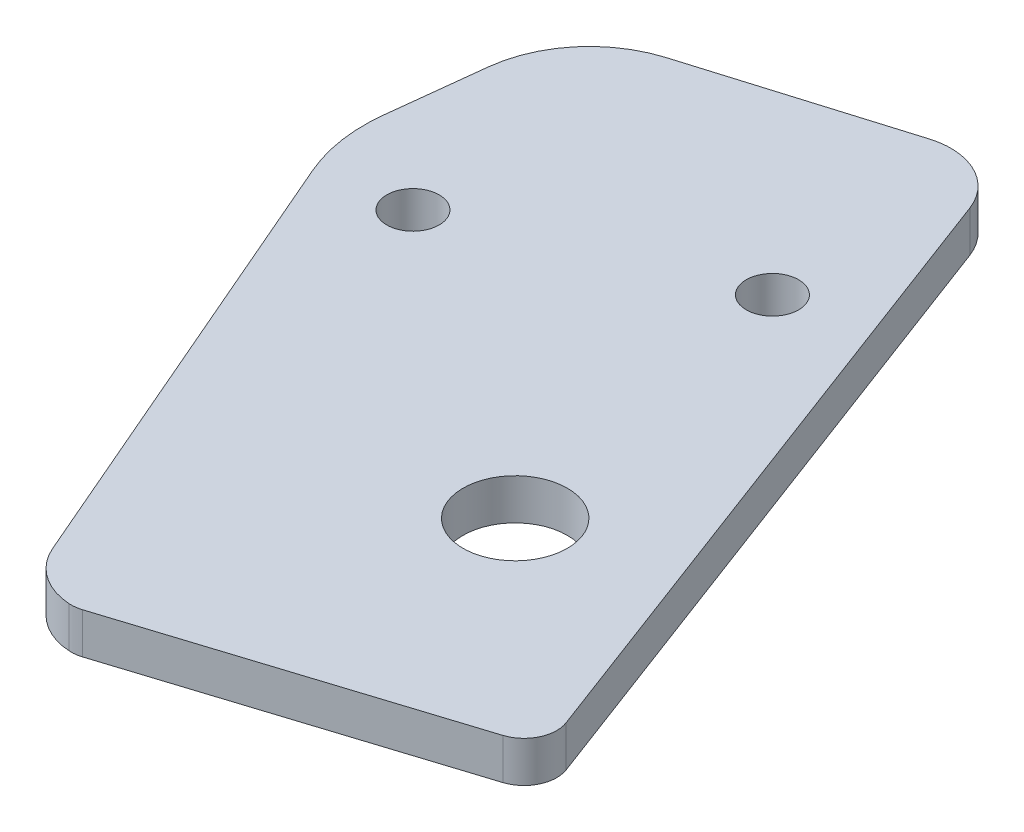
SolidWorks part; units mm, degrees
ref_plane "Front Plane" through (0, 0, 0) normal (0, 0, 1) x (1, 0, 0)
ref_plane "Top Plane" through (0, 0, 0) normal (0, 1, 0) x (1, 0, 0)
ref_plane "Right Plane" through (0, 0, 0) normal (1, 0, 0) x (0, 0, -1)
sketch "Sketch1" plane through (0, 0, 0) normal (0, 1, 0) x (1, 0, 0)
  line L0 (12.7, -6.35) -> (25.4, -6.35)
  line L1 (-12.7, -19.05) -> (12.7, -19.05)
  line L2 (-12.7, -19.05) -> (-12.7, 19.05)
  line L3 (-12.7, 19.05) -> (12.7, 19.05)
  line L4 (12.7, -19.05) -> (12.7, 19.05)
  line L5 (-12.7, -19.05) -> (12.7, 19.05) construction
  line L6 (-12.7, 19.05) -> (12.7, -19.05) construction
  line L7 (25.4, -6.35) -> (25.4, -19.05)
  line L8 (25.4, -19.05) -> (12.7, -19.05)
  point P0 (0, 0)
  dimension "D1" = 25.4
  dimension "D2" = 38.1
  dimension "D3" = 12.7
  dimension "D4" = 12.7
extrude "Boss-Extrude1" add sketch "Sketch1" along normal blind 3.175 contours L1 L4 L3 L2 | L8 L7 L0 L4 region at (19.05, 0, 12.7) region at (0, 0, 0)
sketch "Sketch2" plane through (0, 0, 0) normal (0, -1, 0) x (1, 0, 0)
  line L0 (37.3484, -5.4015) -> (58.4225, -30.0473) construction
  line L1 (58.4225, -30.0473) -> (56.4244, -36.6557) construction
  line L2 (56.4244, -36.6557) -> (28.4937, -28.211) construction
  line L3 (27.672, -14.5925) -> (16.8921, 0.2466) construction
  line L4 (18.9846, 3.1897) -> (28.6818, 0.2578) construction
  line L5 (-33.4925, -38.7551) -> (-34.3249, -31.4398) construction
  line L6 (-33.4148, -25.2954) -> (-18.0647, 10.2749) construction
  line L7 (-1.2058, -33.65) -> (-6.5286, -47.7836) construction
  line L8 (-11.9748, -50.4718) -> (-27.6795, -45.7236) construction
  line L9 (37.3484, -5.4015) -> (58.4225, -30.0473)
  line L10 (58.4225, -30.0473) -> (56.4244, -36.6557)
  line L11 (56.4244, -36.6557) -> (28.4937, -28.211)
  line L12 (27.672, -14.5925) -> (16.8921, 0.2466)
  line L13 (18.9846, 3.1897) -> (28.6818, 0.2578)
  line L14 (-33.4925, -38.7551) -> (-34.3249, -31.4398)
  line L15 (-33.4148, -25.2954) -> (-18.0647, 10.2749)
  line L16 (-1.2058, -33.65) -> (-6.5286, -47.7836)
  line L17 (-11.9748, -50.4718) -> (-27.6795, -45.7236)
  line L18 (-13.3731, 13.4695) -> (19.0101, 3.1818)
  line L20 (-25.2482, -46.4587) -> (-27.4348, -26.2567) construction
  line L21 (-13.0917, -50.1342) -> (-7.7649, -34.5071) construction
  line L22 (-34.9558, -31.5116) -> (-34.1234, -38.8269) construction
  line L23 (-27.8633, -46.3314) -> (-12.1585, -51.0797) construction
  line L24 (-5.9343, -48.0074) -> (-0.6115, -33.8738) construction
  line L25 (-18.6477, 10.5265) -> (-33.9978, -25.0438) construction
  line L26 (-34.9558, -31.5116) -> (-34.1234, -38.8269)
  line L27 (-27.8633, -46.3314) -> (-12.1585, -51.0797)
  line L28 (-5.9343, -48.0074) -> (-0.6115, -33.8738)
  line L29 (-18.6477, 10.5265) -> (-33.9978, -25.0438)
  line L31 (-0.6115, -33.8738) -> (13.9492, 4.7896)
  arc A0 (37.3484, -5.4015) -> (28.6818, 0.2578) centre (23.3524, -17.3692) ccw construction
  arc A1 (27.5335, -25.2281) -> (28.4937, -28.211) centre (29.045, -26.3876) ccw construction
  arc A2 (27.5335, -25.2281) -> (27.672, -14.5925) centre (20.4796, -19.8175) ccw construction
  arc A3 (18.9846, 3.1897) -> (16.8921, 0.2466) centre (18.4333, 1.3662) ccw construction
  arc A4 (-33.4925, -38.7551) -> (-27.6795, -45.7236) centre (-25.2904, -37.8219) ccw construction
  arc A5 (-33.4148, -25.2954) -> (-34.3249, -31.4398) centre (-22.3372, -30.0758) ccw construction
  arc A6 (-14.2611, 12.95) -> (-18.0647, 10.2749) centre (-13.9835, 8.5137) ccw construction
  arc A7 (-13.2163, 9.3838) -> (-14.2611, 12.95) centre (-14.1421, 11.0487) ccw construction
  arc A8 (-13.2163, 9.3838) -> (-2.9671, -31.0738) centre (-2.7239, -9.4851) ccw construction
  arc A9 (-1.2058, -33.65) -> (-2.9671, -31.0738) centre (-2.9886, -32.9786) ccw construction
  arc A10 (-11.9748, -50.4718) -> (-6.5286, -47.7836) centre (-10.6883, -46.2171) ccw construction
  arc A11 (37.3484, -5.4015) -> (28.6818, 0.2578) centre (23.3524, -17.3692) ccw
  arc A12 (27.5335, -25.2281) -> (28.4937, -28.211) centre (29.045, -26.3876) ccw
  arc A13 (27.5335, -25.2281) -> (27.672, -14.5925) centre (20.4796, -19.8175) ccw
  arc A14 (18.9846, 3.1897) -> (16.8921, 0.2466) centre (18.4333, 1.3662) ccw
  arc A15 (-33.4925, -38.7551) -> (-27.6795, -45.7236) centre (-25.2904, -37.8219) ccw
  arc A16 (-33.4148, -25.2954) -> (-34.3249, -31.4398) centre (-22.3372, -30.0758) ccw
  arc A17 (-14.2611, 12.95) -> (-18.0647, 10.2749) centre (-13.9835, 8.5137) ccw
  arc A18 (-13.2163, 9.3838) -> (-14.2611, 12.95) centre (-14.1421, 11.0487) ccw
  arc A19 (-13.2163, 9.3838) -> (-2.9671, -31.0738) centre (-2.7239, -9.4851) ccw
  arc A20 (-1.2058, -33.65) -> (-2.9671, -31.0738) centre (-2.9886, -32.9786) ccw
  arc A21 (-11.9748, -50.4718) -> (-6.5286, -47.7836) centre (-10.6883, -46.2171) ccw
  circle A22 centre (-2.7239, -9.4851) radius 4.05
  circle A23 centre (-7.7649, -34.5071) radius 2.032
  circle A24 centre (-27.4348, -26.2567) radius 2.032
  arc A25 (-34.1234, -38.8269) -> (-27.8633, -46.3314) centre (-25.2904, -37.8219) ccw construction
  arc A26 (-12.1585, -51.0797) -> (-5.9343, -48.0074) centre (-10.6883, -46.2171) ccw construction
  arc A27 (-0.6115, -33.8738) -> (-2.96, -30.4388) centre (-2.9886, -32.9786) ccw construction
  arc A28 (-12.9077, 8.8289) -> (-14.3007, 13.5838) centre (-14.1421, 11.0487) ccw construction
  arc A29 (-14.3007, 13.5838) -> (-18.6477, 10.5265) centre (-13.9835, 8.5137) ccw construction
  arc A30 (-33.9978, -25.0438) -> (-34.9558, -31.5116) centre (-22.3372, -30.0758) ccw construction
  arc A31 (-34.1234, -38.8269) -> (-27.8633, -46.3314) centre (-25.2904, -37.8219) ccw
  arc A32 (-12.1585, -51.0797) -> (-5.9343, -48.0074) centre (-10.6883, -46.2171) ccw
  arc A33 (-0.6115, -33.8738) -> (-2.96, -30.4388) centre (-2.9886, -32.9786) ccw
  arc A34 (-12.9077, 8.8289) -> (-14.3007, 13.5838) centre (-14.1421, 11.0487) ccw
  arc A35 (-14.3007, 13.5838) -> (-18.6477, 10.5265) centre (-13.9835, 8.5137) ccw
  arc A36 (-33.9978, -25.0438) -> (-34.9558, -31.5116) centre (-22.3372, -30.0758) ccw
  point P32 (15.495, 18.8275)
  line M1 (25.4, 19.05) -> (-12.7, 19.05)
  line M2 (-12.7, 19.05) -> (-12.7, -19.05)
  line M3 (-12.7, -19.05) -> (12.7, -19.05)
  line M4 (12.7, -19.05) -> (12.7, 6.35)
  line M5 (12.7, 6.35) -> (25.4, 6.35)
  line M6 (25.4, 6.35) -> (25.4, 19.05)
  dimension "D1" = 8.1
  dimension "D8" = 4.064
  dimension "D2" = 15.24
  dimension "D3" = 16.51
  dimension "D4" = 20.32
  dimension "D5" = 2.54
  dimension "D6" = 67
  dimension "D7" = 92
extrude "Boss-Extrude2" add sketch "Sketch2" against normal blind 3.175 contours L17 A21 L16 A20 A19 A17 L15 A16 L14 A15 M3 M2 | A19 M2 | A20 A19 M3 | L29 A36 L26 A31 L27 A32 L28 A33 A20 L16 A21 L17 A15 L14 A16 L15 A17 A18 A34 A35 M2 | A34 L18 M2 | L31 L18 M4 M5 region at (13.1164, 0, 3.8162) region at (-12.865, 0, 13.2738) region at (-13.8893, 0, -16.3603) region at (-19.8862, 0, -32.0856)
extrude "Cut-Extrude1" cut sketch "Sketch2<3>" against normal through all contours L18 M2 M5 M6 M1 | L31 M3 M4 | A22 region at (8.5325, 0, 13.4044) region at (10.1237, 0, -12.2091) region at (-2.7239, 0, -9.4851)
sketch "Sketch2<3>" plane through (0, 0, 0) normal (0, -1, 0) x (1, 0, 0) same geometry as "Sketch2"
fillet "Fillet1" radius 2.54 1 edges at (13.9492, 1.5875, 4.7896)
